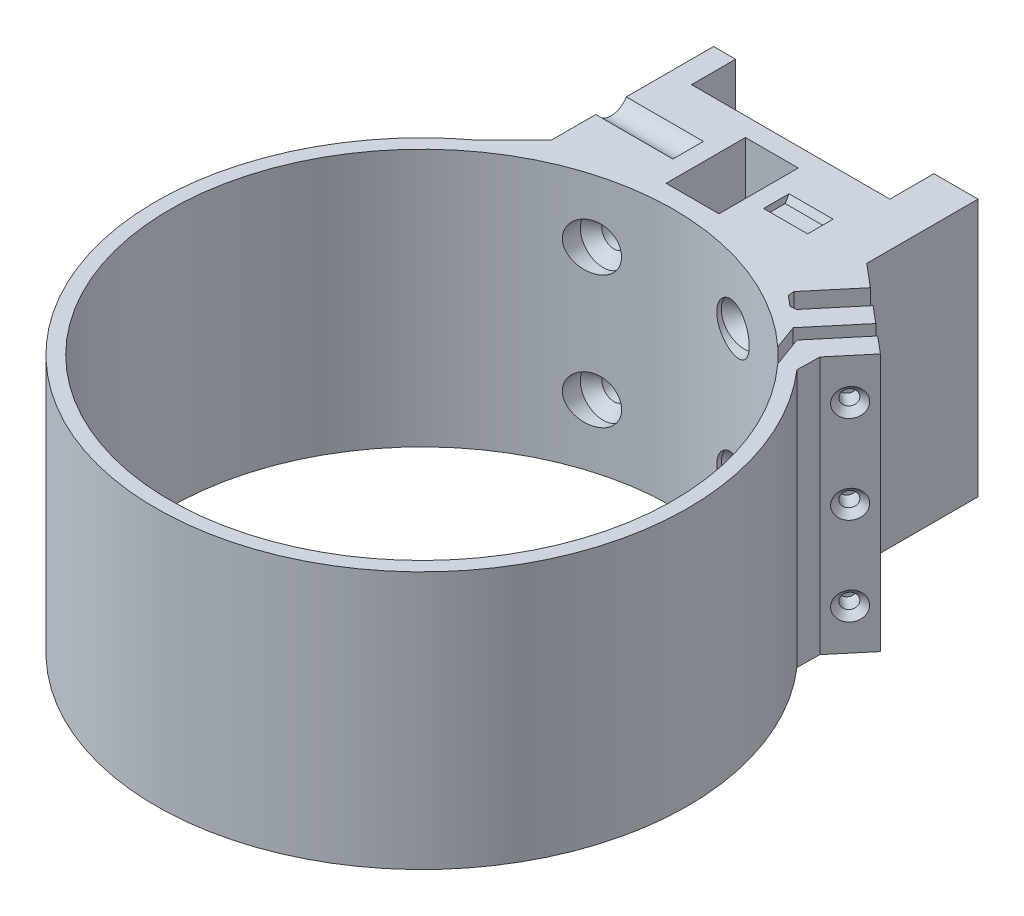
SolidWorks part; units mm, degrees
ref_plane "Front Plane" through (0, 0, 0) normal (0, 0, 1) x (1, 0, 0)
ref_plane "Top Plane" through (0, 0, 0) normal (0, 1, 0) x (1, 0, 0)
ref_plane "Right Plane" through (0, 0, 0) normal (1, 0, 0) x (0, 0, -1)
sketch "Sketch1" plane through (0, 0, 0) normal (0, 1, 0) x (1, 0, 0)
  line L0 (-27.5, 53.6922) -> (-27.5, 93.6922)
  line L5 (-27.5, 93.6922) -> (-22.5, 93.6922)
  line L6 (-22.5, 93.6922) -> (-22.5, 83.6922)
  line L7 (-22.5, 83.6922) -> (22.5, 83.6922)
  line L8 (22.5, 83.6922) -> (22.5, 93.6922)
  line L10 (32.5, 68.4337) -> (32.5, 50.5005) construction
  line L11 (36.7996, 47.4588) -> (38.8013, 41.9593)
  line L12 (39.6559, 45.459) -> (42.1575, 38.5859)
  line L14 (36.7996, 47.4588) -> (45.3513, 57.6503)
  line L15 (39.6559, 45.459) -> (48.0121, 55.4176)
  line L16 (48.0121, 55.4176) -> (51.8423, 52.2036)
  line L17 (51.8423, 52.2036) -> (43.2907, 42.0122)
  line L18 (45.3513, 57.6503) -> (41.521, 60.8642)
  line L19 (41.521, 60.8642) -> (32.9694, 50.6728)
  line L20 (32.9694, 50.6728) -> (29.1392, 53.8867)
  line L21 (29.1392, 53.8867) -> (37.6908, 64.0781)
  line L22 (37.6908, 64.0781) -> (32.5, 68.4337)
  line L23 (22.5, 93.6922) -> (32.5, 93.6922)
  line L24 (32.5, 93.6922) -> (32.5, 68.4337)
  line L26 (-6, 79.4211) -> (6, 79.4211)
  line L27 (-6, 79.4211) -> (-6, 61.4211)
  line L28 (-6, 61.4211) -> (6, 61.4211)
  line L29 (6, 79.4211) -> (6, 61.4211)
  line L30 (0, 57.15) -> (0, 83.6922) construction
  arc A1 (38.8013, 41.9593) -> (42.1575, 38.5859) centre (0, 0) ccw
  arc A2 (36.7996, 47.4588) -> (32.5, 50.5005) centre (0, 0) ccw construction
  arc A3 (43.2907, 42.0122) -> (39.6559, 45.459) centre (0, 0) ccw construction
  arc A4 (-27.5, 53.6922) -> (43.2907, 42.0122) centre (0, 0) ccw
  point P9 (0, 83.6922)
  point P13 (0, 81.6922)
  point P25 (0, 79.4211)
  point P33 (0, 70.4211)
  point P34 (-6, 70.4211)
  dimension "D1" = 114.3
  dimension "D2" = 3.175
  dimension "D3" = 45
  dimension "D4" = 5
  dimension "D5" = 5
  dimension "D6" = 2
  dimension "D7" = 20
  dimension "D8" = 2
  dimension "D9" = 3
  dimension "D10" = 120
  dimension "D11" = 13
  dimension "D12" = 5
  dimension "D13" = 5
  dimension "D14" = 10
  dimension "D15" = 30
  dimension "D16" = 10
  dimension "D17" = 18
  dimension "D18" = 12
extrude "Boss-Extrude1" add sketch "Sketch1" along normal mid plane 58.5
sketch "Sketch4" plane through (0, -29.25, 0) normal (0, -1, 0) x (1, 0, 0)
  line L5 (22.5, -83.6922) -> (-22.5, -83.6922)
  line L6 (22.5, -83.6922) -> (22.5, -93.6922)
  line L7 (22.5, -93.6922) -> (-22.5, -93.6922)
  line L8 (-22.5, -83.6922) -> (-22.5, -93.6922)
extrude "Boss-Extrude2" add sketch "Sketch4" against normal blind 4.5
ref_plane "Plane1" through (0, 0, -57.15) normal (0, 0, 1) x (1, 0, 0)
sketch "Sketch6" plane through (0, 0, -57.15) normal (0, 0, 1) x (1, 0, 0)
  line L1 (16, -15) -> (-16, -15) construction
  line L2 (16, -15) -> (16, 15) construction
  line L3 (16, 15) -> (-16, 15) construction
  line L4 (-16, -15) -> (-16, 15) construction
  line L5 (16, -15) -> (-16, 15) construction
  line L6 (16, 15) -> (-16, -15) construction
  point P0 (0, 0)
  dimension "D1" = 32
  dimension "D2" = 30
hole_wizard "CSK for M5 Flat Head Machine Screw1" positions "Sketch10" profile "Sketch12" countersink size "M5" standard "ANSI Metric" end condition through all
sketch "Sketch10" plane through (0, 0, -57.15) normal (0, 0, 1) x (1, 0, 0)
  point P0 (-16, 15)
  point P3 (16, 15)
  point P6 (16, -15)
  point P9 (-16, -15)
sketch "Sketch12" plane through (-16, 15, -57.15) normal (1, 0, 0) x (0, -1, 0)
  line L0 (0, 0) -> (0, 36.5422)
  line L1 (0, 36.5422) -> (2.75, 36.5422)
  line L2 (2.75, 36.5422) -> (2.75, 2.45)
  line L3 (2.75, 2.45) -> (5.2, 0)
  line L5 (5.2, 0) -> (0, 0)
  line L6 (-2.75, 2.45) -> (-5.2, 0) construction
  line L11 (0, -6.35) -> (0, 107.95) construction
  dimension "Thru Hole Dia." = 5.5
  dimension "Thru Hole Depth" = 36.5422
  dimension "Near C'Sink Dia." = 10.4
  dimension "Near C'Sink Angle" = 90
sketch "Sketch13" plane through (0, 0, -57.15) normal (0, 0, 1) x (1, 0, 0)
  circle A0 centre (-16, -15) radius 5.2 construction
  circle A1 centre (16, -15) radius 5.2 construction
  circle A2 centre (16, 15) radius 5.2 construction
  circle A3 centre (-16, 15) radius 5.2 construction
  circle A4 centre (-16, -15) radius 5.2
  circle A5 centre (16, -15) radius 5.2
  circle A6 centre (16, 15) radius 5.2
  circle A7 centre (-16, 15) radius 5.2
extrude "Cut-Extrude1" cut sketch "Sketch13" along normal up to next
chamfer "Chamfer1" distance 3.175 angle 45 2 edges at (43.2907, 0, -42.0122) (-27.5, 0, -53.6922) first distance on face at (-0.9626, 0, 5.834) first distance on face at (-27.5, 0, -73.6922)
chamfer "Chamfer2" distance 1 angle 45 2 edges at (29.1392, 0, -53.8867) (32.9694, 0, -50.6728)
hole_wizard "CSK for M3 Flat Head Machine Screw1" positions "Sketch2" profile "Sketch3" countersink size "M3" standard "ANSI Metric"
sketch "Sketch2" plane through (4.7171, 0, 3.9581) normal (0.766, 0, 0.6428) x (0.6428, 0, -0.766)
  line L0 (63.5665, 29.25) -> (73.3139, 29.25) construction
  point P0 (68.4402, 20)
  point P2 (68.4402, 0)
  point P4 (68.4402, -20)
  point P16 (68.4402, 29.25)
  dimension "D1" = 20
  dimension "D2" = 20
sketch "Sketch3" plane through (48.7096, 20, -48.4702) normal (0, 1, 0) x (0.6428, 0, -0.766)
  line L0 (0, 0) -> (0, 16.0215)
  line L1 (0, 16.0215) -> (1.7, 15)
  line L2 (1.7, 15) -> (1.7, 1.45)
  line L3 (1.7, 1.45) -> (3.15, 0)
  line L5 (3.15, 0) -> (0, 0)
  line L6 (-1.7, 1.45) -> (-3.15, 0) construction
  line L10 (0, 16.0215) -> (-1.7, 15) construction
  line L11 (0, -6.35) -> (0, 107.95) construction
  dimension "Hole Dia." = 3.4
  dimension "Hole Depth" = 15
  dimension "Near C'Sink Dia." = 6.3
  dimension "Near C'Sink Angle" = 90
  dimension "Drill Angle" = 118
sketch "Sketch14" plane through (-27.5, 0, 0) normal (-1, 0, 0) x (0, 0, 1)
  line L0 (-79.4211, 29.25) -> (-61.4211, 29.25) construction
  line L1 (-79.4211, 29.25) -> (-61.4211, 29.25) construction
  line L2 (-70.4211, 29.25) -> (-70.4211, -29.25) construction
  line L3 (-93.6922, -29.25) -> (-56.8672, -29.25) construction
  point P0 (-70.4211, 0)
  point P7 (-70.4211, 0)
sketch "Sketch17" plane through (-27.5, 0, 0) normal (-1, 0, 0) x (0, 0, 1)
  line L0 (-93.6922, 29.25) -> (-56.8672, 29.25) construction
  line L1 (-70.4211, 31.25) -> (-70.4211, 29.25) construction
  line L2 (-79.4211, 29.25) -> (-61.4211, 29.25) construction
  line L3 (-79.4211, 29.25) -> (-61.4211, 29.25) construction
  circle A0 centre (-70.4211, 31.25) radius 4
  circle A1 centre (-70.4211, 31.25) radius 2 construction
  point P8 (-72.1032, 29.25)
  point P9 (0, 0)
  dimension "D1" = 4
  dimension "D2" = 8
extrude "Cut-Extrude2" cut sketch "Sketch17" against normal offset from surface (17.5 mm away) 4 up to face at (-6, 0, -70.4211)
sketch "Sketch19" plane through (6, 0, 0) normal (-1, 0, 0) x (0, 0, 1)
  line L1 (-68.4004, 34.75) -> (-72.4418, 34.75)
  line L2 (-72.4418, 34.75) -> (-74.4626, 31.25)
  line L3 (-74.4626, 31.25) -> (-72.4418, 27.75)
  line L4 (-72.4418, 27.75) -> (-68.4004, 27.75)
  line L5 (-68.4004, 27.75) -> (-66.3797, 31.25)
  line L6 (-66.3797, 31.25) -> (-68.4004, 34.75)
  circle A0 centre (-70.4211, 31.25) radius 3.5 construction
  circle A1 centre (-70.4211, 31.25) radius 2 construction
  dimension "D1" = 7
extrude "Cut-Extrude3" cut sketch "Sketch19" against normal blind 10 from offset 4 offset against normal yes
mirror "Mirror1" about plane through (0, 0, 0) normal (0, 1, 0) of "Cut-Extrude3", "Cut-Extrude2"
